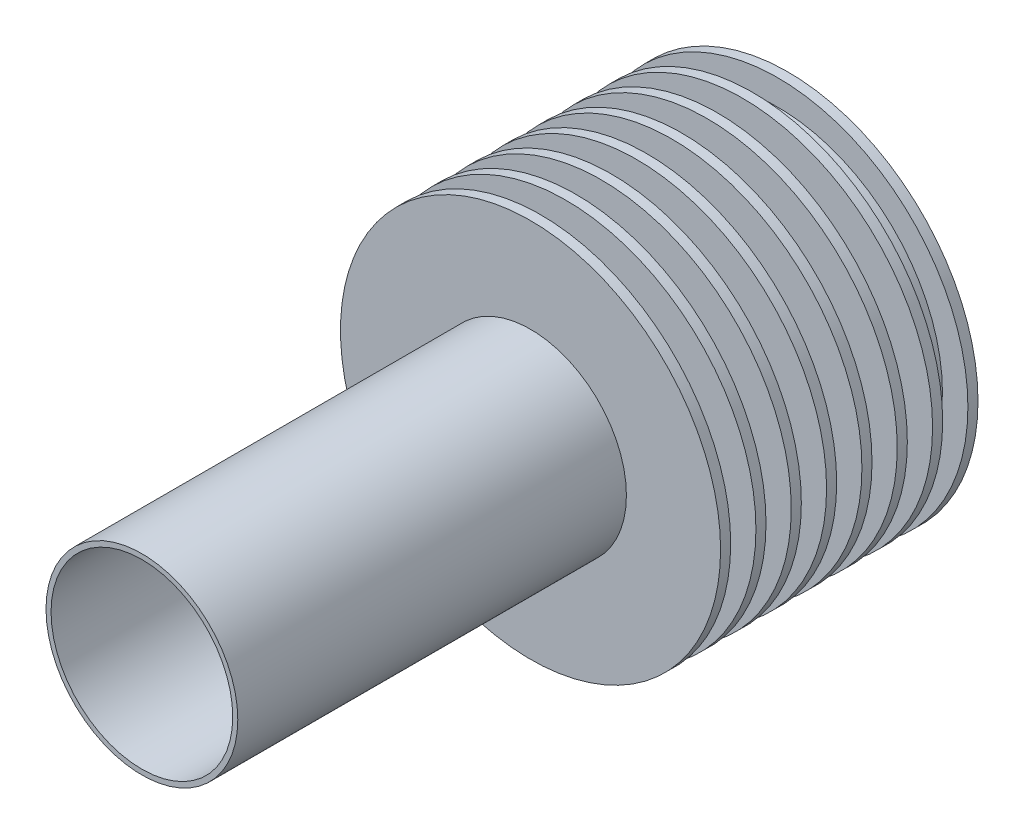
SolidWorks part; units mm, degrees
ref_plane "Front Plane" through (0, 0, 0) normal (0, 0, 1) x (1, 0, 0)
ref_plane "Top Plane" through (0, 0, 0) normal (0, 1, 0) x (1, 0, 0)
ref_plane "Right Plane" through (0, 0, 0) normal (1, 0, 0) x (0, 0, -1)
sketch "Sketch1" plane through (0, 0, 0) normal (0, 0, 1) x (1, 0, 0)
  line L0 (0, 0) -> (-24848.836, 0) construction
  circle A0 centre (0, 0) radius 19
  dimension "D1" = 38
extrude "Boss-Extrude1" add sketch "Sketch1" along normal blind 128
ref_axis "Axis1" through (0, 0, 128) along (0, 0, -1)
sketch "Sketch3" plane through (0, 0, 0) normal (1, 0, 0) x (0, 0, -1)
  line L0 (1042.3835, 19.1576) -> (-2, 19.1576) construction
  line L1 (-128, 19) -> (-128, -19) construction
  line L2 (-51, 19) -> (-51, 50019) construction
  line L3 (-51, 19.1576) -> (-51, 37.6576)
  line L4 (-51, 37.6576) -> (-49, 37.6576)
  line L5 (-49, 37.6576) -> (-49, 19.1576)
  line L6 (-42, 37.6576) -> (-42, 19.1576)
  line L7 (-44, 37.6576) -> (-42, 37.6576)
  line L8 (-44, 19.1576) -> (-44, 37.6576)
  line L9 (-35, 37.6576) -> (-35, 19.1576)
  line L10 (-37, 37.6576) -> (-35, 37.6576)
  line L11 (-37, 19.1576) -> (-37, 37.6576)
  line L12 (-28, 37.6576) -> (-28, 19.1576)
  line L13 (-30, 37.6576) -> (-28, 37.6576)
  line L14 (-30, 19.1576) -> (-30, 37.6576)
  line L15 (-21, 37.6576) -> (-21, 19.1576)
  line L16 (-23, 37.6576) -> (-21, 37.6576)
  line L17 (-23, 19.1576) -> (-23, 37.6576)
  line L18 (-14, 37.6576) -> (-14, 19.1576)
  line L19 (-16, 37.6576) -> (-14, 37.6576)
  line L20 (-16, 19.1576) -> (-16, 37.6576)
  line L21 (-7, 37.6576) -> (-7, 32.6129)
  line L22 (-9, 37.6576) -> (-7, 37.6576)
  line L23 (-9, 19.1576) -> (-9, 37.6576)
  line L24 (0, 37.6576) -> (0, 19.1576)
  line L25 (-2, 37.6576) -> (0, 37.6576)
  line L26 (-2, 32.6129) -> (-2, 37.6576)
  line L27 (-49, 19.1576) -> (-44, 19.1576)
  line L28 (-42, 19.1576) -> (-37, 19.1576)
  line L29 (-35, 19.1576) -> (-30, 19.1576)
  line L30 (-28, 19.1576) -> (-23, 19.1576)
  line L31 (-21, 19.1576) -> (-16, 19.1576)
  line L32 (-14, 19.1576) -> (-9, 19.1576)
  line L34 (-7, 32.6129) -> (-2, 32.6129)
  line L35 (0, 19.1576) -> (0, 18.6576)
  line L36 (0, -19) -> (0, 19) construction
  line L37 (0, 18.6576) -> (-51, 18.6576)
  line L38 (-51, 18.6576) -> (-51, 19.1576)
  line L39 (-7, 19.1576) -> (-50046.3835, 19.1576) construction
  dimension "D1" = 2
  dimension "D2" = 18.5
  dimension "D3" = 77
  dimension "D5" = 0.5
  dimension "D4" = 8
revolve "Revolve1" add sketch "Sketch3" angle 360 about axis through (0, 0, 128) along (0, 0, -1)
sketch "Sketch4" plane through (0, 0, 0) normal (0, 0, -1) x (-1, 0, 0)
  circle A0 centre (0, 0) radius 27.5 construction
  circle A1 centre (0, 27.5) radius 2.5
  circle A2 centre (0, -27.5) radius 2.5
  circle A3 centre (-27.5, 0) radius 2.5
  circle A4 centre (27.5, 0) radius 2.5
  dimension "D1" = 5
  dimension "D2" = 5
  dimension "D3" = 55
  dimension "D4" = 5
  dimension "D5" = 5
extrude "Cut-Extrude1" cut sketch "Sketch4" against normal up to surface (9 mm away) up to face at (19.1576, 0, 9)
hole_wizard "CBORE for M6 Hex Head Bolt1" positions "Sketch5" profile "Sketch6" counterbore size "M6" standard "ISO" end condition through all
sketch "Sketch5" plane through (0, 0, 0) normal (0, 0, -1) x (-1, 0, 0)
  point P0 (0, 0)
sketch "Sketch6" plane through (0, 0, 0) normal (1, 0, 0) x (0, 1, 0)
  line L0 (0, 0) -> (0, 128)
  line L1 (0, 128) -> (18, 128)
  line L3 (18, 128) -> (18, 3)
  line L4 (18, 3) -> (23, 3)
  line L5 (23, 3) -> (23, 0)
  line L7 (23, 0) -> (0, 0)
  line L11 (0, -6.35) -> (0, 107.95) construction
  dimension "Thru Hole Dia." = 36
  dimension "Thru Hole Depth" = 128
  dimension "C'Bore Dia." = 46
  dimension "C'Bore Depth" = 3
thread "Thread1" pitch 0.8 method cut profile "Thread Profile1" start angle 0, offset 0, length 0, pitch 0.8, diameter 5
ref_plane "Plane1" through (2.5, 27.5, 0) normal (0, -1, 0) x (1, 0, 0)
sketch "Thread Profile1" plane through (2.5, 27.5, 0) normal (0, -1, 0) x (1, 0, 0)
  line L0 (0, 0) -> (0, 0.8) construction
  line L1 (0, 0) -> (0.433, 0.25)
  line L2 (0.433, 0.25) -> (0.433, 0.35)
  line L3 (0.433, 0.35) -> (0, 0.6)
  line L4 (0.433, 0.3) -> (0, 0.3) construction
  line L11 (0, 0) -> (0, 0.6)
  point P2 (0, 0)
  dimension "Pitch" = 0.8
  dimension "Profile_Angle" = 60
  dimension "Profile_Land" = 0.1
  dimension "Profile_Height" = 0.433
pattern_circular "CirPattern1" count 4 over 360 about axis through (0, 0, 128) along (0, 0, -1) of "Thread1"
